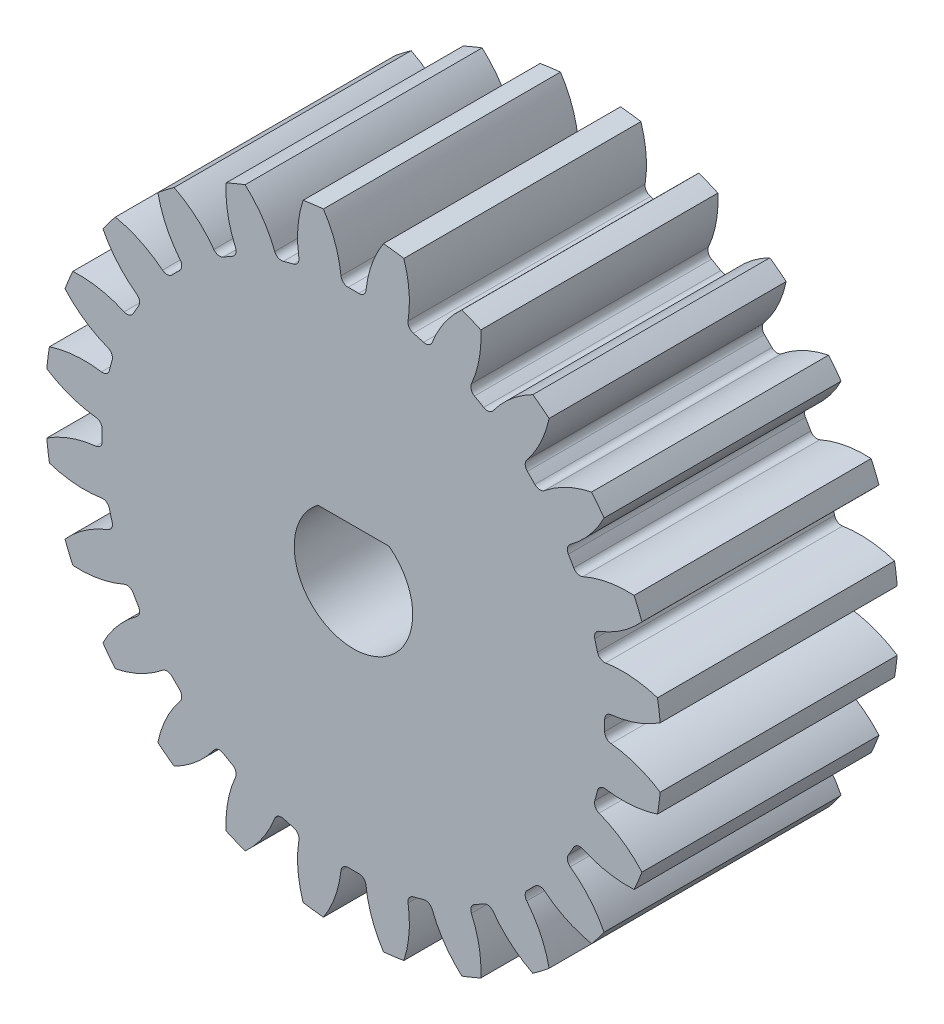
SolidWorks part; units mm, degrees
ref_plane "Front Plane" through (0, 0, 0) normal (0, 0, 1) x (1, 0, 0)
ref_plane "Top Plane" through (0, 0, 0) normal (0, 1, 0) x (1, 0, 0)
ref_plane "Right Plane" through (0, 0, 0) normal (1, 0, 0) x (0, 0, -1)
sketch "Sketch2" plane through (0, 0, 0) normal (0, 0, 1) x (1, 0, 0)
  circle A0 centre (0, 0) radius 12 construction
  circle A1 centre (0, 0) radius 13
  dimension "D1" = 24
  dimension "D2" = 26
extrude "Boss-Extrude1" add sketch "Sketch2" along normal mid plane 10 contours A1
sketch "Sketch3" plane through (0, 0, 0) normal (0, 0, 1) x (1, 0, 0)
  line L0 (0, 13) -> (0, 0) construction
  line L1 (0, 0) -> (3.3646, 12.557) construction
  line L2 (0, 0) -> (1.6968, 12.8888) construction
  line L3 (-0.5061, 10.5879) -> (0, 0) construction
  line L4 (-0.7848, 11.9743) -> (0.7848, 11.9743) construction
  line L5 (0.7848, 11.9743) -> (2.3411, 11.7694) construction
  line L6 (-1.1399, 12.9499) -> (0, 9.818) construction
  circle A0 centre (0, 0) radius 11 construction
  arc A1 (0.5061, 10.5879) -> (-0.5061, 10.5879) centre (0, 0) ccw
  circle A2 centre (0, 0) radius 13 construction
  circle A3 centre (0, 0) radius 12 construction
  arc A4 (-1.2668, 12.9381) -> (-0.5061, 10.5879) centre (-5.2119, 10.363) cw
  arc A5 (1.2668, 12.9381) -> (0.5061, 10.5879) centre (5.2119, 10.363) ccw
  arc A6 (1.2668, 12.9381) -> (-1.2668, 12.9381) centre (0, 0) ccw
  dimension "D4" = 24
  dimension "D1" = 15
  dimension "D2" = 2
  dimension "D3" = 2.4
  dimension "D5" = 20
extrude "Cut-Extrude1" cut sketch "Sketch3" against normal through all both and the other way through all
fillet "Fillet1" radius 0.3 2 edges at (0.5061, 10.5879, 0) (-0.5061, 10.5879, 0)
ref_axis "Axis1" through (0, 0, -11) along (0, 0, 1)
pattern_circular "CirPattern1" count 24 over 360 about axis through (0, 0, -11) along (0, 0, 1) of "Cut-Extrude1", "Fillet1"
sketch "Sketch4" plane through (0, 0, -5) normal (0, 0, -1) x (-1, 0, 0)
  line L0 (-1.5, 2) -> (1.5, 2)
  arc A0 (-1.5, 2) -> (1.5, 2) centre (0, 0) ccw
  point P5 (0, 2)
  dimension "D1" = 5
  dimension "D2" = 2
extrude "Cut-Extrude3" cut sketch "Sketch4" against normal blind 10
equation "\"Module\"= 1"
equation "\"Number of teeth\"= 24"
equation "\"pressure angle\"= 20"
equation "\"D1@Sketch2\"=\"Module\"*\"Number of teeth\""
equation "\"D2@Sketch2\"=(\"Number of teeth\"+2) *\"Module\""
equation "\"D1@Sketch3\"=360 /\"Number of teeth\""
equation "\"D2@Sketch3\"=\"Module\"*2"
equation "\"D3@Sketch3\"=\"Module\" *if( \"Module\"=> 1.25,2.25,2.4)"
equation "\"D5@Sketch3\"=\"pressure angle\""
equation "\"D4@Sketch3\"=\"Module\"*\"Number of teeth\""
equation "\"D1@CirPattern1\"=\"Number of teeth\""
equation "\"D1@Fillet1\"=0.3 *\"Module\""
